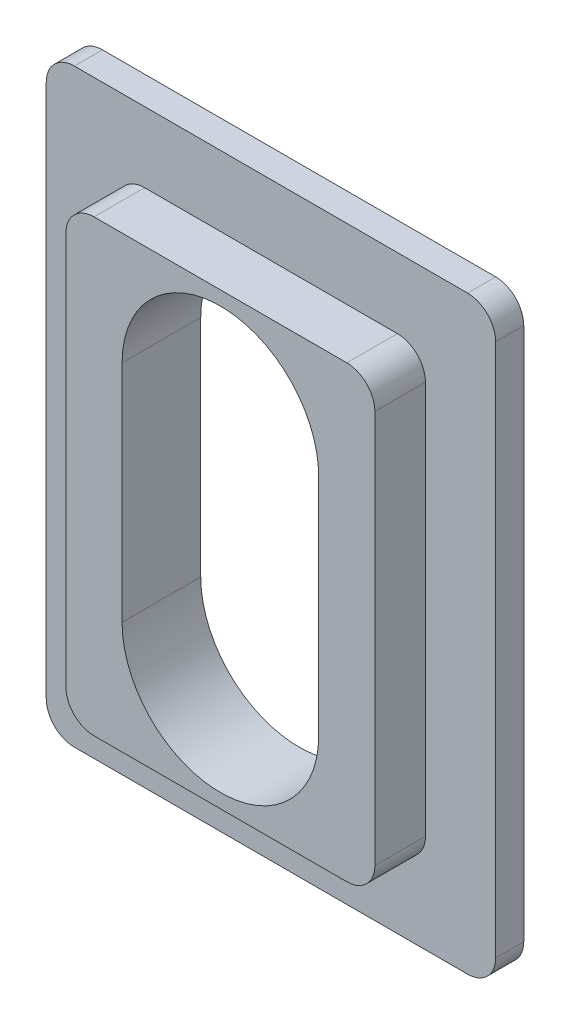
SolidWorks part; units mm, degrees
ref_plane "Plano frontal" through (0, 0, 0) normal (0, 0, 1) x (1, 0, 0)
ref_plane "Plano superior" through (0, 0, 0) normal (0, 1, 0) x (1, 0, 0)
ref_plane "Plano direito" through (0, 0, 0) normal (1, 0, 0) x (0, 0, -1)
sketch "Esboço1" plane through (0, 0, 0) normal (0, 0, 1) x (1, 0, 0)
  line L0 (8, 6.5) -> (8, 14.5) construction
  line L1 (1, 0) -> (15, 0)
  line L2 (0, 1) -> (0, 20)
  line L3 (1, 21) -> (15, 21)
  line L4 (16, 1) -> (16, 20)
  line L5 (3.5, 2.5) -> (12.5, 2.5)
  line L6 (2.5, 3.5) -> (2.5, 17.5)
  line L7 (3.5, 18.5) -> (12.5, 18.5)
  line L8 (13.5, 3.5) -> (13.5, 17.5)
  line L9 (4.5, 6.5) -> (4.5, 14.5)
  line L10 (11.5, 6.5) -> (11.5, 14.5)
  line L11 (8, 2.5) -> (8, 18.5) construction
  line L12 (8, 3) -> (8, 6.5) construction
  line L13 (8, 14.5) -> (8, 18) construction
  arc A0 (12.5, 2.5) -> (13.5, 3.5) centre (12.5, 3.5) ccw
  arc A1 (15, 0) -> (16, 1) centre (15, 1) ccw
  arc A2 (12.5, 18.5) -> (13.5, 17.5) centre (12.5, 17.5) cw
  arc A3 (15, 21) -> (16, 20) centre (15, 20) cw
  arc A4 (2.5, 17.5) -> (3.5, 18.5) centre (3.5, 17.5) cw
  arc A5 (0, 20) -> (1, 21) centre (1, 20) cw
  arc A6 (1, 0) -> (0, 1) centre (1, 1) cw
  arc A7 (3.5, 2.5) -> (2.5, 3.5) centre (3.5, 3.5) cw
  arc A8 (4.5, 6.5) -> (11.5, 6.5) centre (8, 6.5) ccw
  arc A9 (11.5, 14.5) -> (4.5, 14.5) centre (8, 14.5) ccw
  point P23 (0, 0)
  point P28 (8, 10.5)
  point P36 (8, 10.5)
  dimension "D5" = 1
  dimension "D9" = 15
  dimension "D1" = 2.5
  dimension "D2" = 2.5
  dimension "D3" = 2.5
  dimension "D4" = 2.5
  dimension "D6" = 11
  dimension "D7" = 16
  dimension "D8" = 7
extrude "Ressalto-extrusão1" add sketch "Esboço1" along normal blind 1 contours A7 L5 A0 L8 A2 L7 A4 L6 A9 L10 A8 L9 | A6 L1 A1 L4 A3 L3 A5 L2 L5 A7 L6 A4 L7 A2 L8 A0 region at (0.4796, 0.4796, 0) region at (2.9302, 2.9302, 0)
extrude "Ressalto-extrusão3" add sketch "Esboço1<4>" along normal blind 2.8 contours A7 L5 A0 L8 A2 L7 A4 L6 A9 L10 A8 L9 region at (2.9302, 2.9302, 0)
sketch "Esboço1<4>" plane through (0, 0, 0) normal (0, 0, 1) x (1, 0, 0) same geometry as "Esboço1"
